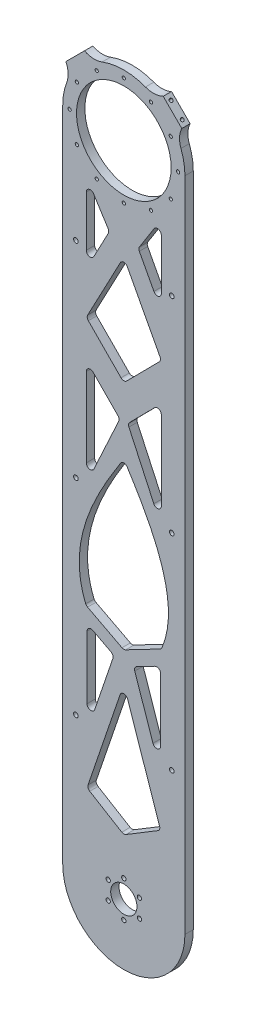
SolidWorks part; units mm, degrees
material "1060 Alloy"
ref_plane "Front Plane" through (0, 0, 0) normal (0, 0, 1) x (1, 0, 0)
ref_plane "Top Plane" through (0, 0, 0) normal (0, 1, 0) x (1, 0, 0)
ref_plane "Right Plane" through (0, 0, 0) normal (1, 0, 0) x (0, 0, -1)
sketch "Sketch2" plane through (0, 0, 0) normal (0, 0, 1) x (1, 0, 0)
  line L0 (0, 0) -> (0, 500) construction
  line L1 (-46.5, 0) -> (-46.5, 500)
  line L2 (46.5, 0) -> (46.5, 500)
  arc A0 (-46.5, 0) -> (46.5, 0) centre (0, 0) ccw
  arc A1 (46.5, 500) -> (-46.5, 500) centre (0, 500) ccw
  circle A2 centre (0, 500) radius 37.25 construction
  circle A3 centre (0, 0) radius 10
  circle A4 centre (0, 13.75) radius 1.65
  circle A5 centre (0, 0) radius 13.75 construction
  circle A6 centre (11.9078, 6.875) radius 1.65
  circle A7 centre (11.9078, -6.875) radius 1.65
  circle A8 centre (0, -13.75) radius 1.65
  circle A9 centre (-11.9078, -6.875) radius 1.65
  circle A10 centre (-11.9078, 6.875) radius 1.65
  point P3 (0, 250)
  point P27 (0, 0)
  dimension "D2" = 74.5
  dimension "D4" = 20
  dimension "D5" = 3.3
  dimension "D6" = 27.5
  dimension "D3" = 46.5
  dimension "D1" = 500
  dimension "D7" = 6
extrude "Boss-Extrude1" add sketch "Sketch2" along normal blind 6.35
sketch "Sketch4" plane through (0, 0, 6.35) normal (0, 0, 1) x (1, 0, 0)
  line L0 (0, 500) -> (0, 999.1647) construction
  line L29 (46.5, 500) -> (-46.5, 500) construction
  line L31 (28.0053, 59.376) -> (0, 42.4117)
  line L32 (0, 141.6934) -> (28.0053, 59.376)
  line L33 (-28.0053, 59.376) -> (0, 141.6934)
  line L34 (0, 42.4117) -> (-28.0053, 59.376)
  line L35 (-7.5, 156.9059) -> (-28.0053, 96.6336)
  line L36 (-28.0053, 167.5829) -> (-7.5, 156.9059)
  line L37 (-28.0053, 96.6336) -> (-28.0053, 167.5829)
  line L38 (28.0053, 167.5829) -> (7.5, 156.9059)
  line L39 (28.0053, 96.6336) -> (28.0053, 167.5829)
  line L40 (7.5, 156.9059) -> (28.0053, 96.6336)
  line L41 (0, 164.2751) -> (28.5505, 179.1412)
  line L42 (0, 164.2751) -> (-28.5505, 179.1412)
  line L43 (28.5505, 259.5868) -> (3, 314.9383)
  line L44 (28.5505, 340.7931) -> (28.5505, 259.5868)
  line L45 (3, 314.9383) -> (28.5505, 340.7931)
  line L46 (-3, 314.9383) -> (-28.5505, 340.7931)
  line L47 (-28.5505, 259.5868) -> (-3, 314.9383)
  line L48 (-28.5505, 340.7931) -> (-28.5505, 259.5868)
  line L49 (0, 423.1428) -> (-28.5505, 369.2462)
  line L50 (-28.5505, 369.2462) -> (0, 340.3557)
  line L51 (0, 340.3557) -> (28.5505, 369.2462)
  line L52 (0, 423.1428) -> (28.5505, 369.2462)
  line L53 (-28.5505, 462.0952) -> (-28.5505, 401.2902)
  line L54 (-11, 434.4215) -> (-28.5505, 462.0952)
  line L55 (-28.5505, 401.2902) -> (-11, 434.4215)
  line L56 (28.5505, 401.2902) -> (11, 434.4215)
  line L57 (28.5505, 462.0952) -> (28.5505, 401.2902)
  line L58 (11, 434.4215) -> (28.5505, 462.0952)
  arc A0 (46.5, 500) -> (-46.5, 500) centre (0, 500) ccw construction
  arc A1 (46.5, 500) -> (-46.5, 500) centre (0, 500) ccw construction
  spline S2 degree 3 poles (28.5505, 179.1412) (45.3203, 216.9857) (19.4301, 259.7903) (0, 290.0258) knots 0 0 0 0 1 1 1 1
  spline S3 degree 3 poles (-28.5505, 179.1412) (-45.3203, 216.9857) (-19.4301, 259.7903) (0, 290.0258) knots 0 0 0 0 1 1 1 1
extrude "Cut-Extrude1" cut sketch "Sketch4" against normal blind 10
fillet "Fillet3" radius 3 30 edges at (-11, 434.4215, 3.175) (-28.5505, 401.2902, 3.175) (28.5505, 401.2902, 3.175) (11, 434.4215, 3.175) (28.5505, 462.0952, 3.175) (-28.5505, 462.0952, 3.175) (0, 423.1428, 3.175) (-28.5505, 369.2462, 3.175) (28.5505, 369.2462, 3.175) (0, 340.3557, 3.175) (28.5505, 340.7931, 3.175) (-28.5505, 340.7931, 3.175) (-3, 314.9383, 3.175) (3, 314.9383, 3.175) (28.5505, 259.5868, 3.175) (-28.5505, 259.5868, 3.175) (28.5505, 179.1412, 3.175) (0, 290.0258, 3.175) (-28.5505, 179.1412, 3.175) (0, 164.2751, 3.175) (-28.0053, 96.6336, 3.175) (28.0053, 96.6336, 3.175) (7.5, 156.9059, 3.175) (-28.0053, 167.5829, 3.175) (28.0053, 167.5829, 3.175) (0, 141.6934, 3.175) (28.0053, 59.376, 3.175) (-28.0053, 59.376, 3.175) (0, 42.4117, 3.175) (-7.5, 156.9059, 3.175)
sketch "Sketch5" plane through (0, 0, 6.35) normal (0, 0, 1) x (1, 0, 0)
  line L0 (0, -46.5) -> (108.8395, -46.5) construction
  line L1 (46.5, 100) -> (-46.5, 100) construction
  line L2 (46.5, 0) -> (46.5, 500) construction
  line L3 (-46.5, 500) -> (-46.5, 0) construction
  line L4 (-46.5, 106.35) -> (46.5, 106.35) construction
  line L5 (36.5, 106.35) -> (36.5, 100) construction
  line L6 (0, 106.35) -> (0, 100) construction
  line L7 (-46.5, 256.35) -> (46.5, 256.35) construction
  line L8 (-46.5, 181.35) -> (46.5, 181.35) construction
  line L9 (-46.5, 337.7) -> (46.5, 337.7) construction
  arc A1 (-46.5, 0) -> (46.5, 0) centre (0, 0) ccw construction
  circle A2 centre (36.5, 103.175) radius 1.75
  circle A3 centre (-36.5, 103.175) radius 1.75
  circle A4 centre (36.5, 259.525) radius 1.75
  circle A5 centre (-36.5, 259.525) radius 1.75
  circle A6 centre (36.5, 415.875) radius 1.75
  circle A7 centre (-36.5, 415.875) radius 1.75
  point P18 (36.5, 103.175)
  dimension "D2" = 3.5
  dimension "D1" = 146.5
  dimension "D3" = 10
  dimension "D4" = 6.35
  dimension "D5" = 150
  dimension "D6" = 81.35
  dimension "D7" = 81.35
extrude "Cut-Extrude2" cut sketch "Sketch5" against normal through all
sketch "Sketch6" plane through (0, 0, 6.35) normal (0, 0, 1) x (1, 0, 0)
  circle A0 centre (0, 500) radius 26.5
  arc A1 (46.5, 500) -> (-46.5, 500) centre (0, 500) ccw construction
  arc A2 (46.5, 500) -> (-46.5, 500) centre (0, 500) ccw construction
  dimension "D1" = 20
extrude "Cut-Extrude3" cut sketch "Sketch6" against normal blind 10
sketch "Sketch7" plane through (0, 0, 6.35) normal (0, 0, 1) x (1, 0, 0)
  line L1 (40.0163, 523.6842) -> (44.1104, 529.9682) construction
  line L2 (23.6842, 540.0163) -> (29.9682, 544.1104) construction
  line L3 (44.1104, 529.9682) -> (29.9682, 544.1104)
  line L4 (0, 500) -> (37.0393, 537.0393) construction
  line L5 (0, 500) -> (0, 546.5) construction
  arc A0 (46.5, 500) -> (-46.5, 500) centre (0, 500) ccw construction
  arc A1 (29.9682, 544.1104) -> (16.4747, 543.4837) centre (22.4977, 559.381) cw
  arc A2 (44.1104, 529.9682) -> (43.4837, 516.4747) centre (59.381, 522.4977) ccw
  arc A3 (16.4747, 543.4837) -> (43.4837, 516.4747) centre (0, 500) cw
  dimension "D3" = 17
  dimension "D5" = 17
  dimension "D1" = 20
  dimension "D2" = 7.5
  dimension "D4" = 8
  dimension "D6" = 8
  dimension "D7" = 45
extrude "Boss-Extrude2" add sketch "Sketch7" against normal up to surface (6.35 mm away) up to face at (26.5, 500, 0)
sketch "Sketch8" plane through (287.0393, 287.0393, 0) normal (0.7071, 0.7071, 0) x (0, 0, -1)
  line L0 (0, 363.5534) -> (-6.35, 363.5534) construction
  line L1 (0, 343.5534) -> (-6.35, 343.5534) construction
  line L2 (-6.35, 343.5534) -> (-6.35, 363.5534) construction
  point P0 (-3.175, 359.5534)
  point P1 (-3.175, 347.5534)
  dimension "D1" = 4
  dimension "D2" = 4
  dimension "D3" = 3.175
hole_wizard "Tap Drill for M3x0.5 Tap1" positions "Sketch8" profile "Sketch9" hole size "M3x0.5" standard "ANSI Metric"
sketch "Sketch9" plane through (32.7967, 541.282, 3.175) normal (0, 0, 1) x (-0.7071, 0.7071, 0)
  line L0 (0, 0) -> (0, 5.7511)
  line L1 (0, 5.7511) -> (1.25, 5)
  line L2 (1.25, 5) -> (1.25, 0)
  line L5 (1.25, 0) -> (0, 0)
  line L10 (0, 5.7511) -> (-1.25, 5) construction
  line L11 (0, -6.35) -> (0, 107.95) construction
  dimension "Hole Dia." = 2.5
  dimension "Hole Depth" = 5
  dimension "Drill Angle" = 118
pattern_circular "CirPattern2" count 2 every 90 about axis through (0, 500, -3.65) along (0, 0, 1) of "Boss-Extrude2", "Tap Drill for M3x0.5 Tap1"
sketch "Sketch11" plane through (0, 0, 6.35) normal (0, 0, 1) x (1, 0, 0)
  circle A0 centre (0, 500) radius 36
  circle A1 centre (0, 500) radius 26.5 construction
  dimension "D1" = 72
extrude "Cut-Extrude5" cut sketch "Sketch11" against normal through all
sketch "Sketch12" plane through (0, 0, 6.35) normal (0, 0, 1) x (1, 0, 0)
  circle A15 centre (0, 500) radius 41.25 construction
  circle A16 centre (0, 500) radius 36 construction
  circle A17 centre (0, 500) radius 36 construction
  circle A18 centre (0, 541.25) radius 1.25
  dimension "D1" = 82.5
  dimension "D2" = 2.5
extrude "Cut-Extrude6" cut sketch "Sketch12" against normal through all both and the other way through all
pattern_circular "CirPattern3" count 12 over 360 about axis through (0, 500, 0) along (0, 0, 1) of "Cut-Extrude6"
equation "\"L1L\"=500"
equation "\"L1Thick\"=6.35"
equation "\"D1@Sketch2\"=\"L1L\""
equation "\"Harm-Drive-Outer\"=74.5"
equation "\"D2@Sketch2\"=\"Harm-Drive-Outer\""
equation "\"D1@Boss-Extrude1\"=\"L1Thick\""
